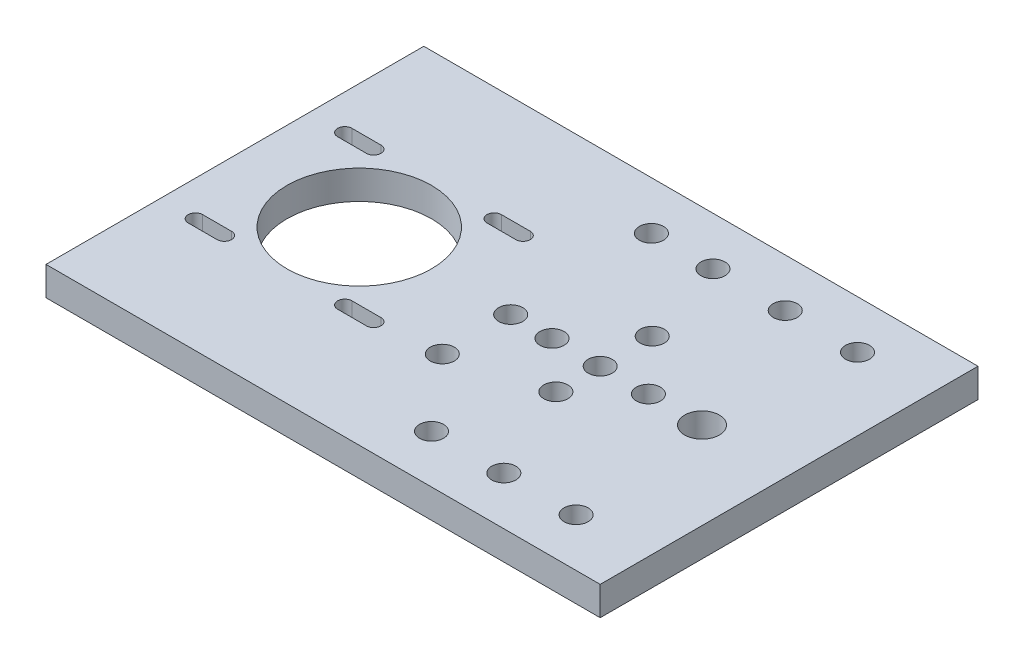
SolidWorks part; units mm, degrees
ref_plane "Front Plane" through (0, 0, 0) normal (0, 0, 1) x (1, 0, 0)
ref_plane "Top Plane" through (0, 0, 0) normal (0, 1, 0) x (1, 0, 0)
ref_plane "Right Plane" through (0, 0, 0) normal (1, 0, 0) x (0, 0, -1)
sketch "Sketch1" plane through (0, 0, 0) normal (0, 1, 0) x (1, 0, 0)
  line L0 (21.1312, 14.1992) -> (21.1312, -14.1992) construction
  line L1 (-39.1992, 39.1992) -> (39.1992, 39.1992) construction
  line L2 (-39.1992, 39.1992) -> (-39.1992, -39.1992) construction
  line L3 (-39.1992, -39.1992) -> (39.1992, -39.1992) construction
  line L4 (39.1992, 39.1992) -> (39.1992, -39.1992) construction
  line L5 (-39.1992, 39.1992) -> (39.1992, -39.1992) construction
  line L6 (-39.1992, -39.1992) -> (39.1992, 39.1992) construction
  line L7 (-5.8008, 29.1992) -> (9.1992, 29.1992) construction
  line L8 (-5.8008, -29.1992) -> (9.1992, -29.1992) construction
  line L9 (9.1992, 29.1992) -> (24.1992, 29.1992) construction
  line L10 (24.1992, 29.1992) -> (39.1992, 29.1992) construction
  line L11 (9.1992, -29.1992) -> (24.1992, -29.1992) construction
  line L12 (24.1992, -29.1992) -> (39.1992, -29.1992) construction
  line L39 (39.1992, -39.1992) -> (39.1992, 39.1992)
  line L40 (39.1992, 39.1992) -> (-75.8008, 39.1992)
  line L41 (-75.8008, 39.1992) -> (-75.8008, -39.1992)
  line L42 (-75.8008, -39.1992) -> (-39.1992, -39.1992)
  line L43 (-39.1992, -39.1992) -> (39.1992, -39.1992)
  line L44 (-65.5, -15.5) -> (-34.5, -15.5) construction
  line L45 (-65.5, -15.5) -> (-65.5, 15.5) construction
  line L46 (-65.5, 15.5) -> (-34.5, 15.5) construction
  line L47 (-34.5, -15.5) -> (-34.5, 15.5) construction
  line L48 (-65.5, -15.5) -> (-34.5, 15.5) construction
  line L49 (-65.5, 15.5) -> (-34.5, -15.5) construction
  line L50 (-68.5, 14) -> (-62.5, 14)
  line L52 (-68.5, 17) -> (-62.5, 17)
  line L54 (-68.5, 14) -> (-62.5, 17) construction
  line L55 (-68.5, 17) -> (-62.5, 14) construction
  line L56 (-37.5, 14) -> (-31.5, 14)
  line L58 (-37.5, 17) -> (-31.5, 17)
  line L60 (-37.5, 14) -> (-31.5, 17) construction
  line L61 (-37.5, 17) -> (-31.5, 14) construction
  line L62 (-37.5, -17) -> (-31.5, -17)
  line L64 (-37.5, -14) -> (-31.5, -14)
  line L66 (-37.5, -17) -> (-31.5, -14) construction
  line L67 (-37.5, -14) -> (-31.5, -17) construction
  line L68 (-68.5, -17) -> (-62.5, -17)
  line L70 (-68.5, -14) -> (-62.5, -14)
  line L72 (-68.5, -17) -> (-62.5, -14) construction
  line L73 (-68.5, -14) -> (-62.5, -17) construction
  circle A0 centre (-18.5688, 29.1992) radius 2.5
  circle A1 centre (-18.5688, -14.1992) radius 2.5
  circle A2 centre (24.1992, 29.1992) radius 2.5
  circle A3 centre (9.1992, 29.1992) radius 2.5
  circle A4 centre (21.1312, 0) radius 3.6
  circle A5 centre (0, 0) radius 2.5
  circle A6 centre (-10, 0) radius 2.5
  circle A7 centre (-18.5688, 0) radius 2.5
  circle A8 centre (10, 0) radius 2.5
  circle A9 centre (-5.8008, 29.1992) radius 2.5
  circle A10 centre (-5.8008, -29.1992) radius 2.5
  circle A11 centre (24.1992, -29.1992) radius 2.5
  circle A12 centre (9.1992, -29.1992) radius 2.5
  circle A13 centre (0, -9.1992) radius 2.5
  circle A14 centre (0, 10.8008) radius 2.5
  circle A15 centre (-50, 0) radius 15
  arc A16 (-68.5, 17) -> (-68.5, 14) centre (-68.5, 15.5) ccw
  arc A17 (-62.5, 17) -> (-62.5, 14) centre (-62.5, 15.5) cw
  arc A18 (-37.5, 17) -> (-37.5, 14) centre (-37.5, 15.5) ccw
  arc A19 (-31.5, 17) -> (-31.5, 14) centre (-31.5, 15.5) cw
  arc A20 (-31.5, -14) -> (-31.5, -17) centre (-31.5, -15.5) cw
  arc A21 (-37.5, -14) -> (-37.5, -17) centre (-37.5, -15.5) ccw
  arc A22 (-62.5, -14) -> (-62.5, -17) centre (-62.5, -15.5) cw
  arc A23 (-68.5, -14) -> (-68.5, -17) centre (-68.5, -15.5) ccw
  point P0 (0, 0)
  point P15 (21.1312, 0)
  dimension "D1" = 5
  dimension "D9" = 30
  dimension "D11" = 1.5
  dimension "D7" = 10
  dimension "D15" = 25
  dimension "D5" = 5
  dimension "D2" = 10
  dimension "D3" = 10
  dimension "D4" = 10
  dimension "D6" = 10
  dimension "D8" = 115
  dimension "D10" = 31
  dimension "D12" = 6
  dimension "D13" = 8.5688
  dimension "D14" = 11.1312
  dimension "D16" = 50
  dimension "D17" = 78.3985
  dimension "D18" = 15
extrude "Boss-Extrude1" add sketch "Sketch1" along normal blind 6 contours L40 L41 L42 L43 L39
extrude "Cut-Extrude3" cut sketch "Sketch1<7>" along normal blind 6 contours A15 | A18 L56 A19 L58 | A17 L50 A16 L52 | A22 L68 A23 L70 | A20 L62 A21 L64 | A7 | A0 | A4 | A1 | A6 | A5 | A13 | A8 | A14 | A3 | A2 | A11 | A12 | A10 | A9
sketch "Sketch1<7>" plane through (0, 0, 0) normal (0, 1, 0) x (1, 0, 0) same geometry as "Sketch1"
